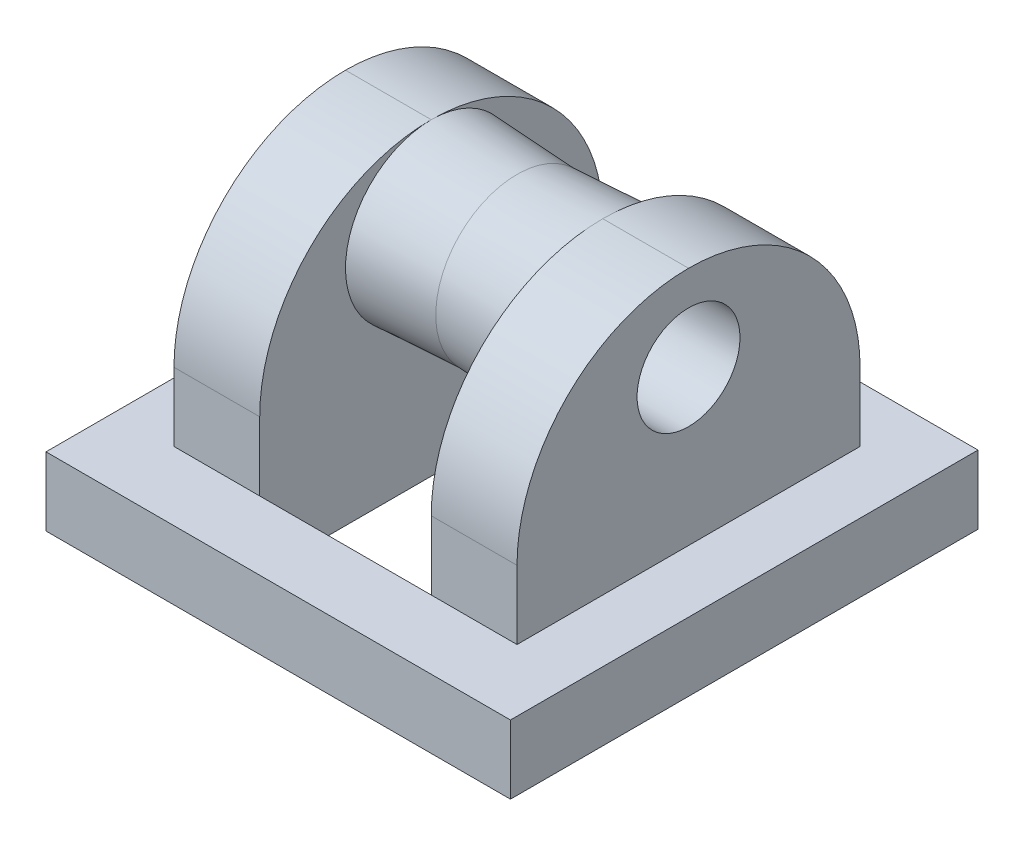
SolidWorks part; units mm, degrees
material "ABS"
ref_plane "Front Plane" through (0, 0, 0) normal (0, 0, 1) x (1, 0, 0)
ref_plane "Top Plane" through (0, 0, 0) normal (0, 1, 0) x (1, 0, 0)
ref_plane "Right Plane" through (0, 0, 0) normal (1, 0, 0) x (0, 0, -1)
sketch "Sketch1" plane through (0, 0, 0) normal (0, 0, 1) x (1, 0, 0)
  line L0 (0, 0) -> (60, 0)
  line L1 (60, 0) -> (80, 20)
  line L2 (80, 20) -> (80, 115)
  line L3 (80, 115) -> (58, 115)
  line L4 (-10, 105) -> (11, 105)
  line L5 (-10, 105) -> (-10, 25)
  line L6 (-10, 25) -> (0, 0)
  line L7 (57, 115) -> (57, 114)
  line L8 (35, 115) -> (57, 115)
  line L9 (34, 115) -> (34, 110)
  line L10 (35, 115) -> (34, 115)
  line L11 (34, 110) -> (12, 110)
  line L12 (12, 110) -> (11, 110)
  line L13 (11, 110) -> (11, 105)
  line L14 (57, 115) -> (58, 115)
  line L15 (57, 114) -> (58, 114)
  line L16 (58, 114) -> (58, 115)
  dimension "D1" = 60
  dimension "D2" = 22
  dimension "D3" = 90
  dimension "D4" = 20
  dimension "D5" = 80
  dimension "D6" = 95
  dimension "D7" = 135
  dimension "D8" = 1
  dimension "D9" = 22
  dimension "D10" = 22
  dimension "D11" = 1
  dimension "D12" = 5
  dimension "D13" = 1
  dimension "D14" = 5
  dimension "D15" = 1
extrude "Boss-Extrude1" add sketch "Sketch1" along normal blind 20 contours L16 L15 L7 L8 L10 L9 L11 L12 L13 L4 L5 L6 L0 L1 L2 L3 region at (35.6394, 57.3872, 0)
sketch "Sketch2" plane through (0, 0, 20) normal (0, 0, 1) x (1, 0, 0)
  line L0 (80, 30) -> (60, 30)
  line L2 (60, 30) -> (60, 60)
  line L3 (60, 60) -> (80, 60)
  line L4 (80, 60) -> (80, 30)
  dimension "D1" = 20
  dimension "D2" = 10
  dimension "D3" = 30
extrude "Cut-Extrude1" cut sketch "Sketch2" against normal through all
shell "Shell1" thickness 2 removed face at (44.4444, 74.6111, 20)
sketch "Sketch42" plane through (0, 0, 2) normal (0, 0, 1) x (1, 0, 0)
  line L1 (56.2697, 82) -> (55, 82)
  line L2 (56.2697, 82) -> (56.2697, 112)
  line L3 (56.2697, 112) -> (55, 112)
  line L4 (55, 82) -> (55, 112)
  dimension "D1" = 30
extrude "Boss-Extrude16" add sketch "Sketch42" along normal blind 15
sketch "Sketch37" plane through (78, 0, 0) normal (-1, 0, 0) x (0, 0, 1)
  line L0 (2, 105) -> (13.5, 105)
  line L1 (2, 65) -> (2, 113) construction
  line L2 (20, 113) -> (2, 113) construction
  dimension "D1" = 8
  dimension "D2" = 11.5
sketch "Sketch45" plane through (0, 0, 2) normal (0, 0, 1) x (1, 0, 0)
  line L0 (32.4973, 78) -> (32.4973, 108)
  line L1 (36, 108) -> (13, 108) construction
  line L2 (32.4973, 108) -> (30.4973, 108)
  line L3 (30.4973, 108) -> (30.4973, 78)
  line L4 (30.4973, 78) -> (32.4973, 78)
  dimension "D1" = 30
  dimension "D2" = 2
extrude "Boss-Extrude17" add sketch "Sketch45" along normal blind 15
sketch "Sketch40" plane through (78, 0, 0) normal (1, 0, 0) x (0, 0, -1)
  circle A0 centre (-13.5, 105) radius 1.25
  dimension "D1" = 2.5
extrude "Cut-Extrude15" cut sketch "Sketch40" along normal blind 1 and the other way blind 51
sketch "Sketch41" plane through (58, 0, 0) normal (-1, 0, 0) x (0, 0, 1)
  line L29 (15, 65) -> (15, 25)
  line L30 (15, 55) -> (15, 35)
  line L32 (7, 65) -> (7, 25)
  line L33 (7, 55) -> (7, 35)
  line L35 (2, 55) -> (20, 55)
  line L36 (7, 55) -> (15, 55)
  line L38 (2, 35) -> (20, 35)
  line L39 (7, 35) -> (15, 35)
  dimension "D1" = 5
  dimension "D2" = 5
  dimension "D3" = 10
  dimension "D4" = 10
extrude "Cut-Extrude16" cut sketch "Sketch41" against normal blind 10
sketch "Sketch44" plane through (0, 0, 20) normal (0, 0, 1) x (1, 0, 0)
  line L0 (36, 108) -> (13, 108) construction
  line L1 (36, 113) -> (35, 113)
  line L2 (36, 113) -> (36, 108)
  line L3 (36, 108) -> (35, 108)
  line L4 (35, 113) -> (35, 108)
  dimension "D1" = 1
extrude "Cut-Extrude18" cut sketch "Sketch44" against normal up to surface (18 mm away) up to face at (43.2939, 77.6756, 2)
sketch "Sketch46" plane through (0, 0, 2) normal (0, 0, 1) x (1, 0, 0)
  line L0 (12.0788, 88) -> (12.0788, 89)
  line L1 (12.0788, 89) -> (16.75, 89)
  line L2 (16.75, 89) -> (16.75, 79)
  line L3 (16.75, 79) -> (15.75, 79)
  line L4 (15.75, 79) -> (15.75, 88)
  line L5 (15.75, 88) -> (12.0788, 88)
  dimension "D1" = 1
  dimension "D2" = 1
  dimension "D3" = 10
extrude "Boss-Extrude18" add sketch "Sketch46" along normal blind 15
sketch "Sketch47" plane through (-8, 0, 0) normal (1, 0, 0) x (0, 0, -1)
  circle A0 centre (-13.5, 95) radius 1.1
  dimension "D1" = 2.2
extrude "Cut-Extrude19" cut sketch "Sketch47" against normal blind 1 and the other way blind 44.5
sketch "Sketch50" plane through (0, 0, 2) normal (0, 0, 1) x (1, 0, 0)
  line L0 (33, 57.4) -> (33, 59.4)
  line L1 (33, 59.4) -> (58, 59.4)
  line L2 (58, 65) -> (58, 25) construction
  line L3 (58, 59.4) -> (58, 57.4)
  line L4 (58, 57.4) -> (33, 57.4)
  line L5 (33, 57.4) -> (33.0839, 57.2104)
  line M16 (58, 25) -> (58, 65)
  dimension "D1" = 2
  dimension "D2" = 25
extrude "Boss-Extrude19" add sketch "Sketch50" along normal blind 15 contours L4 L1 L0 M16 region at (45.5, 58.4, 2)
sketch "Sketch51" plane through (0, 0, 2) normal (0, 0, 1) x (1, 0, 0)
  line L0 (58, 35) -> (58, 33)
  line L1 (58, 57.4) -> (58, 25) construction
  line L2 (58, 33) -> (47.0246, 33)
  line L3 (47.0246, 33) -> (47.0246, 35)
  line L4 (47.0246, 35) -> (58, 35)
  line M33 (58, 25) -> (58, 57.4)
  dimension "D1" = 2
  dimension "D2" = 0
extrude "Boss-Extrude20" add sketch "Sketch51" along normal blind 15 contours L4 L3 L2 M33 region at (52.5123, 34, 2)
sketch "Sketch52" plane through (0, 0, 2) normal (0, 0, 1) x (1, 0, 0)
  line L0 (42.7484, 49.4) -> (43.7484, 49.4)
  line L1 (43.7484, 49.4) -> (43.7484, 44.4)
  line L2 (43.7484, 44.4) -> (33.7484, 44.4)
  line L3 (33.7484, 44.4) -> (33.7484, 45.4)
  line L4 (33.7484, 45.4) -> (42.7484, 45.4)
  line L5 (42.7484, 45.4) -> (42.7484, 49.4)
  line L6 (40.4973, 97.2126) -> (40.4973, 98.2126)
  line L7 (40.4973, 98.2126) -> (45.4973, 98.2126)
  line L8 (45.4973, 98.2126) -> (45.4973, 88.2126)
  line L9 (45.4973, 88.2126) -> (44.4973, 88.2269)
  line L10 (44.4973, 88.2269) -> (44.4973, 97.2126)
  line L11 (44.4973, 97.2126) -> (40.4973, 97.2126)
  line L12 (64.2697, 97.2269) -> (64.2697, 98.2269)
  line L13 (64.2697, 98.2269) -> (69.2697, 98.2269)
  line L14 (69.2697, 98.2269) -> (69.2697, 88.2269)
  line L15 (69.2697, 88.2269) -> (68.2697, 88.2269)
  line L16 (68.2697, 88.2269) -> (68.2697, 97.2269)
  line L17 (68.2697, 97.2269) -> (64.2697, 97.2269)
  dimension "D1" = 10
  dimension "D2" = 1
  dimension "D3" = 1
  dimension "D4" = 5
  dimension "D5" = 5
  dimension "D6" = 10
  dimension "D7" = 1
  dimension "D8" = 1
  dimension "D9" = 10
  dimension "D10" = 5
  dimension "D11" = 1
  dimension "D12" = 1
extrude "Boss-Extrude21" add sketch "Sketch52" along normal blind 5
sketch "Sketch53" plane through (0, 57.4, 0) normal (0, -1, 0) x (1, 0, 0)
  circle A0 centre (49, 13.5) radius 1.1
  dimension "D1" = 2.2
extrude "Cut-Extrude21" cut sketch "Sketch53" against normal blind 1 and the other way blind 33.5
sketch "Sketch34" plane through (0, 65, 0) normal (0, 1, 0) x (1, 0, 0)
  line L0 (58, -2) -> (58, -20) construction
  line L1 (78, -2) -> (58, -2) construction
  circle A0 centre (70, -11) radius 2.5
  dimension "D3" = 5
  dimension "D1" = 12
  dimension "D2" = 9
extrude "Cut-Extrude14" cut sketch "Sketch34" against normal up to surface (40 mm away) up to face at (68, 25, 11)
sketch "Sketch3" plane through (0, 115, 0) normal (0, 1, 0) x (1, 0, 0)
  line L1 (80, 0) -> (58, 0) construction
  line L2 (74, -8) -> (64, -8)
  line L3 (74, -8) -> (74, -18)
  line L4 (74, -18) -> (64, -18)
  line L5 (64, -8) -> (64, -18)
  line L6 (74, -8) -> (64, -18) construction
  line L7 (74, -18) -> (64, -8) construction
  line L8 (66.5, -8) -> (66.5, -18)
  line L9 (71.5, -8) -> (71.5, -18)
  point P0 (69, -13)
  dimension "D1" = 10
  dimension "D2" = 10
  dimension "D3" = 5
  dimension "D4" = 2.5
  dimension "D5" = 13
extrude "Boss-Extrude2" add sketch "Sketch3" along normal blind 7 contours L8 L2 L5 L4 | L2 L9 L4 L3 region at (72.75, 115, 13) region at (65.25, 115, 13)
fillet "Fillet2" radius 5 4 edges at (65.25, 122, 8) (65.25, 122, 18) (72.75, 122, 8) (72.75, 122, 18)
sketch "Sketch6" plane through (74, 0, 0) normal (1, 0, 0) x (0, 0, -1)
  circle A0 centre (-13, 119.5) radius 1.5
  dimension "D1" = 3
  dimension "D2" = 2.5
  dimension "D3" = 0
extrude "Cut-Extrude3" cut sketch "Sketch6" against normal up to surface (10 mm away) up to face at (64, 117.6142, 13)
sketch "Sketch21" plane through (66.5, 0, 0) normal (1, 0, 0) x (0, 0, -1)
  circle A0 centre (-13, 119.5) radius 1.5
  circle A1 centre (-13, 119.5) radius 2.5
  circle M1 centre (-13, 119.5) radius 1.5
  dimension "D1" = 5
extrude "Boss-Extrude10" add sketch "Sketch21" along normal blind 2.5 draft 3 contours A1 M1 region at (66.5, 119.5, 15.4293)
mirror "Mirror7" about plane through (69, 0, 0) normal (1, 0, 0) of "Boss-Extrude10"
sketch "Sketch26" plane through (0, 115, 0) normal (0, 1, 0) x (1, 0, 0)
  line L1 (66.5, -18) -> (71.5, -18)
  line L2 (66.5, -18) -> (66.5, -8)
  line L3 (66.5, -8) -> (71.5, -8)
  line L4 (71.5, -18) -> (71.5, -8)
  dimension "D1" = 5
  dimension "D2" = 10
extrude "Cut-Extrude8" cut sketch "Sketch26" against normal up to surface (2 mm away) up to face at (69, 113, 11)
sketch "Sketch7" plane through (0, 115, 0) normal (0, 1, 0) x (1, 0, 0)
  line L0 (50, -8) -> (40, -8)
  line L1 (50, -8) -> (50, -18)
  line L2 (50, -18) -> (40, -18)
  line L3 (40, -8) -> (40, -18)
  line L4 (50, -8) -> (40, -18) construction
  line L5 (50, -18) -> (40, -8) construction
  line L6 (42.5, -8) -> (42.5, -18)
  line L7 (47.5, -8) -> (47.5, -18)
  line L10 (34, 0) -> (57, 0) construction
  point P0 (45, -13)
  dimension "D1" = 10
  dimension "D2" = 10
  dimension "D3" = 5
  dimension "D4" = 2.5
  dimension "D5" = 13
extrude "Boss-Extrude4" add sketch "Sketch7" along normal blind 5 contours L6 L0 L3 L2 | L0 L7 L2 L1 region at (48.75, 115, 13) region at (41.25, 115, 13)
fillet "Fillet4" radius 5 4 edges at (41.25, 120, 8) (41.25, 120, 18) (48.75, 120, 8) (48.75, 120, 18)
sketch "Sketch22" plane through (42.5, 0, 0) normal (1, 0, 0) x (0, 0, -1)
  circle A0 centre (-13, 117.5) radius 2.5
  dimension "D1" = 5
  dimension "D2" = 2.5
  dimension "D3" = 0
extrude "Boss-Extrude11" add sketch "Sketch22" along normal blind 2.5 draft 3
mirror "Mirror8" about plane through (45, 117.5, 13) normal (1, 0, 0) of "Boss-Extrude11"
sketch "Sketch23" plane through (50, 0, 0) normal (1, 0, 0) x (0, 0, -1)
  circle A0 centre (-13, 117.5) radius 1.5
  dimension "D3" = 3
  dimension "D1" = 0
  dimension "D2" = 2.5
extrude "Cut-Extrude7" cut sketch "Sketch23" against normal up to surface (10 mm away) up to face at (40, 117.357, 13)
sketch "Sketch27" plane through (0, 115, 0) normal (0, 1, 0) x (1, 0, 0)
  line L1 (42.5, -18) -> (47.5, -18)
  line L2 (42.5, -18) -> (42.5, -8)
  line L3 (42.5, -8) -> (47.5, -8)
  line L4 (47.5, -18) -> (47.5, -8)
  dimension "D1" = 5
  dimension "D2" = 10
extrude "Cut-Extrude9" cut sketch "Sketch27" against normal up to surface (2 mm away)
sketch "Sketch10" plane through (0, 110, 0) normal (0, 1, 0) x (1, 0, 0)
  line L0 (28, -8) -> (18, -8)
  line L1 (28, -8) -> (28, -18)
  line L2 (28, -18) -> (18, -18)
  line L3 (18, -8) -> (18, -18)
  line L4 (28, -8) -> (18, -18) construction
  line L5 (28, -18) -> (18, -8) construction
  line L6 (20.5, -8) -> (20.5, -18)
  line L7 (25.5, -8) -> (25.5, -18)
  line L8 (34, 0) -> (11, 0) construction
  line L10 (34, -20) -> (34, 0) construction
  point P0 (23, -13)
  point P11 (22.5, 0)
  dimension "D1" = 10
  dimension "D2" = 10
  dimension "D3" = 5
  dimension "D4" = 2.5
  dimension "D5" = 13
  dimension "D6" = 11
extrude "Boss-Extrude6" add sketch "Sketch10" along normal blind 5 contours L6 L0 L3 L2 | L0 L7 L2 L1 region at (26.75, 110, 13) region at (19.25, 110, 13)
fillet "Fillet6" radius 5 4 edges at (19.25, 115, 18) (19.25, 115, 8) (26.75, 115, 8) (26.75, 115, 18)
sketch "Sketch28" plane through (20.5, 0, 0) normal (1, 0, 0) x (0, 0, -1)
  circle A0 centre (-13, 112.5) radius 2.5
  dimension "D3" = 5
  dimension "D1" = 2.5
  dimension "D2" = 0
extrude "Boss-Extrude12" add sketch "Sketch28" along normal blind 2.5 draft 3
mirror "Mirror9" about plane through (23, 112.5, 13) normal (1, 0, 0) of "Boss-Extrude12"
sketch "Sketch29" plane through (28, 0, 0) normal (1, 0, 0) x (0, 0, -1)
  circle A0 centre (-13, 112.5) radius 1.5
  dimension "D3" = 3
  dimension "D1" = 2.5
  dimension "D2" = 0
extrude "Cut-Extrude10" cut sketch "Sketch29" against normal up to surface (10 mm away) up to face at (18, 112.357, 13)
sketch "Sketch30" plane through (0, 110, 0) normal (0, 1, 0) x (1, 0, 0)
  line L1 (20.5, -18) -> (25.5, -18)
  line L2 (20.5, -18) -> (20.5, -8)
  line L3 (20.5, -8) -> (25.5, -8)
  line L4 (25.5, -18) -> (25.5, -8)
  dimension "D1" = 5
  dimension "D2" = 10
extrude "Cut-Extrude11" cut sketch "Sketch30" against normal up to surface (2 mm away)
sketch "Sketch13" plane through (0, 105, 0) normal (0, 1, 0) x (1, 0, 0)
  line L0 (6, -8) -> (-4, -8)
  line L1 (6, -8) -> (6, -18)
  line L2 (6, -18) -> (-4, -18)
  line L3 (-4, -8) -> (-4, -18)
  line L4 (6, -8) -> (-4, -18) construction
  line L5 (6, -18) -> (-4, -8) construction
  line L6 (-1.5, -8) -> (-1.5, -18)
  line L7 (3.5, -8) -> (3.5, -18)
  line L8 (-10, 0) -> (11, 0) construction
  line L9 (-10, -20) -> (-10, 0) construction
  point P0 (1, -13)
  dimension "D1" = 10
  dimension "D2" = 10
  dimension "D3" = 5
  dimension "D4" = 2.5
  dimension "D5" = 13
  dimension "D6" = 11
extrude "Boss-Extrude8" add sketch "Sketch13" along normal blind 5 contours L6 L0 L3 L2 | L0 L7 L2 L1 region at (4.75, 105, 13) region at (-2.75, 105, 13)
fillet "Fillet8" radius 5 4 edges at (-2.75, 110, 18) (-2.75, 110, 8) (4.75, 110, 8) (4.75, 110, 18)
sketch "Sketch31" plane through (-1.5, 0, 0) normal (1, 0, 0) x (0, 0, -1)
  circle A0 centre (-13, 107.5) radius 2.5
  dimension "D3" = 5
  dimension "D1" = 2.5
  dimension "D2" = 0
extrude "Boss-Extrude13" add sketch "Sketch31" along normal blind 2.5 draft 3
mirror "Mirror10" about plane through (1, 107.5, 13) normal (1, 0, 0) of "Boss-Extrude13"
sketch "Sketch32" plane through (6, 0, 0) normal (1, 0, 0) x (0, 0, -1)
  circle A0 centre (-13, 107.5) radius 1.5
  dimension "D2" = 3
  dimension "D1" = 2.5
extrude "Cut-Extrude12" cut sketch "Sketch32" against normal up to surface (10 mm away) up to face at (-4, 107.357, 13)
sketch "Sketch33" plane through (0, 105, 0) normal (0, 1, 0) x (1, 0, 0)
  line L1 (-1.5, -8) -> (3.5, -8)
  line L2 (-1.5, -8) -> (-1.5, -18)
  line L3 (-1.5, -18) -> (3.5, -18)
  line L4 (3.5, -8) -> (3.5, -18)
  dimension "D1" = 5
  dimension "D2" = 10
extrude "Cut-Extrude13" cut sketch "Sketch33" against normal up to surface (2 mm away) up to face at (2.5, 103, 11)
ref_plane "Plane1" through (-10, 105, 0) normal (0, -1, 0) x (-1, 0, 0)
sketch "Sketch55" plane through (0, 0, 0) normal (0, 0, -1) x (-1, 0, 0)
  line L1 (-62.2696, 135.3207) -> (45.7225, 135.3207)
  line L2 (-62.2696, 135.3207) -> (-62.2696, -16.7272)
  line L3 (-62.2696, -16.7272) -> (45.7225, -16.7272)
  line L4 (45.7225, 135.3207) -> (45.7225, -16.7272)
extrude "Cut-Extrude22" cut sketch "Sketch55" against normal through all
sketch "Sketch57" plane through (0, 0, 0) normal (0, 0, -1) x (-1, 0, 0)
  line L1 (-62.2696, 113) -> (-86.7922, 113)
  line L2 (-62.2696, 113) -> (-62.2696, -2.4447)
  line L3 (-62.2696, -2.4447) -> (-86.7922, -2.4447)
  line L4 (-86.7922, 113) -> (-86.7922, -2.4447)
extrude "Cut-Extrude23" cut sketch "Sketch57" against normal through all
sketch "Sketch58" plane through (0, 115, 0) normal (0, 1, 0) x (1, 0, 0)
  line L0 (62.2696, 0) -> (62.2696, -20) construction
  line L1 (80, 0) -> (62.2696, 0)
  line L2 (80, 0) -> (80, -6.3709)
  line L3 (75.8088, -6.3709) -> (62.2696, -6.3709)
  line L4 (62.2696, 0) -> (62.2696, -6.3709)
  line L6 (80, -20) -> (75.8088, -20)
  line L7 (80, -20) -> (80, -6.3709)
  line L9 (75.8088, -20) -> (75.8088, -6.3709)
extrude "Cut-Extrude24" cut sketch "Sketch58" against normal through all
